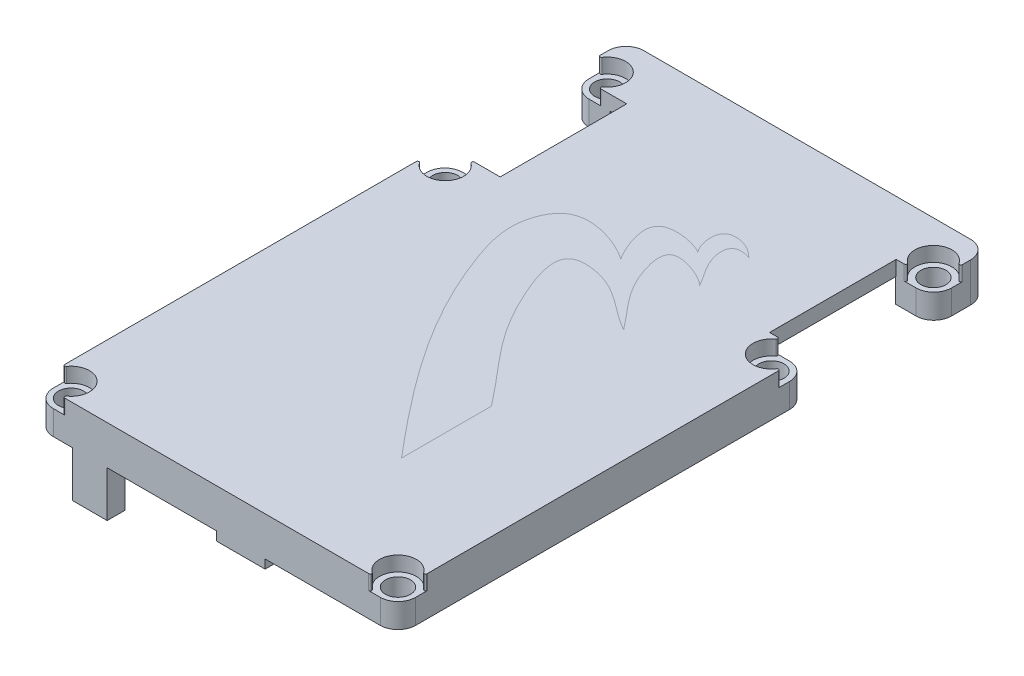
SolidWorks part; units mm, degrees
ref_plane "Front Plane" through (0, 0, 0) normal (0, 0, 1) x (1, 0, 0)
ref_plane "Top Plane" through (0, 0, 0) normal (0, 1, 0) x (1, 0, 0)
ref_plane "Right Plane" through (0, 0, 0) normal (1, 0, 0) x (0, 0, -1)
sketch "Sketch1" plane through (0, 0, 0) normal (0, 1, 0) x (1, 0, 0)
  line L1 (0, 0) -> (49.1, 0)
  line L2 (0, 0) -> (0, -80)
  line L3 (0, -80) -> (49.1, -80)
  line L4 (49.1, 0) -> (49.1, -80)
  dimension "D1" = 80
  dimension "D2" = 49.1
extrude "Boss-Extrude1" add sketch "Sketch1" along normal blind 2
sketch "Sketch2" plane through (0, 2, 0) normal (0, 1, 0) x (1, 0, 0)
  line L0 (49.1, 0) -> (0, 0) construction
  line L1 (2.45, -5) -> (46.65, -5) construction
  line L2 (2.45, -5) -> (2.45, -26.95) construction
  line L3 (2.45, -26.95) -> (46.65, -26.95) construction
  line L4 (46.65, -5) -> (46.65, -26.95) construction
  line L5 (0, 0) -> (0, -80) construction
  line L6 (24.55, -5) -> (24.55, 0) construction
  line L7 (0, -80) -> (49.1, -80) construction
  line L8 (24.55, -80) -> (24.55, -37.9836) construction
  circle A0 centre (2.4, -77.6) radius 1.7
  circle A1 centre (2.45, -26.95) radius 1.7
  circle A2 centre (2.45, -5) radius 1.7
  circle A3 centre (46.7, -77.6) radius 1.7
  circle A4 centre (46.65, -26.95) radius 1.7
  circle A5 centre (46.65, -5) radius 1.7
  dimension "D5" = 3.4
  dimension "D6" = 2.4
  dimension "D7" = 2.4
  dimension "D1" = 5
  dimension "D2" = 21.95
  dimension "D3" = 44.2
extrude "Cut-Extrude1" cut sketch "Sketch2" against normal blind 2
sketch "Sketch3" plane through (0, 0, 0) normal (0, -1, 0) x (1, 0, 0)
  line L0 (24.55, 80) -> (24.55, 0) construction
  line L1 (0, 80) -> (5.2, 80)
  line L2 (0, 80) -> (0, 74.8)
  line L3 (0, 74.8) -> (5.2, 74.8)
  line L4 (5.2, 80) -> (5.2, 74.8)
  line L5 (0, 80) -> (49.1, 80) construction
  line L6 (49.1, 0) -> (0, 0) construction
  line L7 (2.45, 26.95) -> (2.45, 5) construction
  line L8 (2.45, 15.975) -> (24.55, 15.975) construction
  line L9 (0, 0) -> (0, 80) construction
  line L10 (5.2, 29.75) -> (0, 29.75)
  line L11 (5.2, 29.75) -> (5.2, 24.55)
  line L12 (5.2, 24.55) -> (0, 24.55)
  line L13 (0, 29.75) -> (0, 24.55)
  line L16 (5.2, 7.4) -> (0, 2.2) construction
  line L17 (5.2, 2.2) -> (0, 7.4) construction
  line L18 (0, 2.2) -> (0, 7.4)
  line L19 (5.2, 7.4) -> (0, 7.4)
  line L20 (5.2, 2.2) -> (5.2, 7.4)
  line L21 (5.2, 2.2) -> (0, 2.2)
  line L22 (43.9, 2.2) -> (49.1, 7.4) construction
  line L23 (43.9, 7.4) -> (49.1, 2.2) construction
  line L24 (43.9, 24.55) -> (49.1, 29.75) construction
  line L25 (43.9, 29.75) -> (49.1, 24.55) construction
  line L26 (46.65, 26.95) -> (46.65, 5) construction
  line L27 (43.9, 2.2) -> (49.1, 2.2)
  line L28 (43.9, 2.2) -> (43.9, 7.4)
  line L29 (43.9, 7.4) -> (49.1, 7.4)
  line L30 (49.1, 2.2) -> (49.1, 7.4)
  line L31 (49.1, 29.75) -> (49.1, 24.55)
  line L32 (43.9, 24.55) -> (49.1, 24.55)
  line L33 (43.9, 29.75) -> (43.9, 24.55)
  line L34 (43.9, 29.75) -> (49.1, 29.75)
  line L35 (43.9, 80) -> (43.9, 74.8)
  line L36 (49.1, 74.8) -> (43.9, 74.8)
  line L37 (49.1, 80) -> (49.1, 74.8)
  line L38 (49.1, 80) -> (43.9, 80)
  circle A0 centre (2.4, 77.6) radius 1.7
  circle A1 centre (2.4, 77.6) radius 1.7 construction
  circle A2 centre (2.45, 26.95) radius 1.7
  circle A3 centre (2.45, 26.95) radius 1.7 construction
  circle A4 centre (2.45, 5) radius 1.7
  circle A5 centre (46.65, 5) radius 1.7
  circle A6 centre (46.65, 26.95) radius 1.7
  circle A7 centre (46.7, 77.6) radius 1.7
  dimension "D1" = 5.2
  dimension "D2" = 2.4
  dimension "D3" = 2.8
  dimension "D4" = 5.2
  dimension "D5" = 5.2
extrude "Boss-Extrude2" add sketch "Sketch3" along normal blind 3.3
sketch "Sketch4" plane through (0, 2, 0) normal (0, 1, 0) x (1, 0, 0)
  line L0 (0, 0) -> (0, -80) construction
  line L1 (0, -7.4) -> (7.5, -7.4)
  line L2 (0, -7.4) -> (0, -24.55)
  line L3 (0, -24.55) -> (7.5, -24.55)
  line L4 (7.5, -7.4) -> (7.5, -24.55)
  line L5 (2.45, -5) -> (2.45, -26.95) construction
  line L6 (2.45, -15.975) -> (7.5, -15.975) construction
  line L7 (49.1, -80) -> (49.1, 0) construction
  line L8 (49.1, -7.4) -> (44, -7.4)
  line L9 (49.1, -7.4) -> (49.1, -24.55)
  line L10 (49.1, -24.55) -> (44, -24.55)
  line L11 (44, -7.4) -> (44, -24.55)
  line L12 (44, -15.975) -> (7.5, -15.975) construction
  line L13 (5.2, -7.4) -> (0, -7.4) construction
  dimension "D1" = 7.5
  dimension "D4" = 5.1
extrude "Cut-Extrude2" cut sketch "Sketch4" against normal blind 3.3
sketch "Sketch6" plane through (0, 0, 0) normal (0, -1, 0) x (1, 0, 0)
  line L0 (49.1, 46.0108) -> (0, 46.0108) construction
  line L5 (11.8806, 53.3353) -> (37.2194, 53.3353)
  line L6 (11.8806, 53.3353) -> (11.8806, 38.6862)
  line L7 (11.8806, 38.6862) -> (37.2194, 38.6862)
  line L8 (37.2194, 53.3353) -> (37.2194, 38.6862)
  line L9 (11.8806, 53.3353) -> (37.2194, 38.6862) construction
  line L10 (11.8806, 38.6862) -> (37.2194, 53.3353) construction
  line L11 (49.1, 74.8) -> (49.1, 29.75) construction
  line L12 (0, 29.75) -> (0, 74.8) construction
  line L13 (24.55, 80) -> (24.55, 12.0215) construction
  line L14 (5.2, 80) -> (43.9, 80) construction
  point P4 (24.55, 46.0108)
extrude "Boss-Extrude3" [suppressed] add sketch "Sketch6" along normal blind 3.2
sketch "Sketch7" plane through (0, 0, 0) normal (0, -1, 0) x (1, 0, 0)
  line L1 (5.2, 80) -> (43.9, 80)
  line L2 (5.2, 80) -> (5.2, 77.6)
  line L3 (5.2, 77.6) -> (43.9, 77.6)
  line L4 (43.9, 80) -> (43.9, 77.6)
  line L6 (46.7, 74.8) -> (49.1, 74.8)
  line L7 (46.7, 74.8) -> (46.7, 29.75)
  line L8 (46.7, 29.75) -> (49.1, 29.75)
  line L9 (49.1, 74.8) -> (49.1, 29.75)
  line L11 (2.4, 74.8) -> (0, 74.8)
  line L12 (2.4, 74.8) -> (2.4, 29.75)
  line L13 (2.4, 29.75) -> (0, 29.75)
  line L14 (0, 74.8) -> (0, 29.75)
  line L15 (49.1, 2.2) -> (49.1, 0) construction
  line L16 (0, 0) -> (49.1, 0)
  line L17 (0, 0) -> (0, 2)
  line L18 (5.2, 2) -> (43.9, 2)
  line L19 (49.1, 0) -> (49.1, 2)
  line L20 (5.2, 2.2) -> (5.2, 7.4) construction
  line L21 (0, 2.2) -> (5.2, 2.2)
  line L22 (0, 2.2) -> (0, 2)
  line L24 (5.2, 2.2) -> (5.2, 2)
  line L25 (0, 2.2) -> (5.2, 2.2) construction
  line L26 (0, 74.8) -> (5.2, 74.8) construction
  line L28 (49.1, 2) -> (49.1, 2.2)
  line L29 (49.1, 2.2) -> (43.9, 2.2)
  line L30 (43.9, 2) -> (43.9, 2.2)
  line L31 (43.9, 74.8) -> (49.1, 74.8) construction
  dimension "D1" = 2
  dimension "D2" = 2
  dimension "D3" = 2.4
  dimension "D4" = 2.4
  dimension "D5" = 2.4
extrude "Boss-Extrude4" add sketch "Sketch7" along normal up to surface (3.3 mm away) up to face at (46.5, -3.3, 27.15)
sketch "Sketch8" plane through (0, 0, 80) normal (0, 0, 1) x (1, 0, 0)
  line L0 (49.1, -3.3) -> (0, -3.3) construction
  line L1 (24.5, -3.3) -> (31.1, -3.3)
  line L2 (24.5, -3.3) -> (24.5, -4.5)
  line L3 (24.5, -4.5) -> (31.1, -4.5)
  line L4 (31.1, -3.3) -> (31.1, -4.5)
  line L6 (27.8, -4.5) -> (27.8, 0) construction
  line L7 (49.1, 2) -> (49.1, -3.3) construction
  line L8 (5, -3.3) -> (9.7, -3.3)
  line L9 (5, -3.3) -> (5, -9.5)
  line L10 (5, -9.5) -> (9.7, -9.5)
  line L11 (9.7, -3.3) -> (9.7, -9.5)
  line L12 (7.35, -9.5) -> (7.35, 5.3073) construction
  line L13 (0, 2) -> (0, -3.3) construction
  dimension "D1" = 1.2
  dimension "D2" = 6.6
  dimension "D3" = 21.3
  dimension "D4" = 6.2
  dimension "D5" = 7.35
  dimension "D6" = 4.7
extrude "Boss-Extrude5" add sketch "Sketch8" against normal up to surface (2.4 mm away) up to face at (24.55, -1.65, 77.6)
fillet "Fillet1" radius 2.4 8 edges at (0, -0.65, 24.55) (0, -0.65, 7.4) (0, -0.65, 0) (49.1, -0.65, 0) (49.1, -0.65, 80) (0, -0.65, 80) (49.1, -0.65, 7.4) (49.1, -0.65, 24.55)
sketch "Sketch9" plane through (0, 2, 0) normal (0, 1, 0) x (1, 0, 0)
  line L0 (24.55, 0) -> (24.55, -80) construction
  line L1 (46.7, 0) -> (2.4, 0) construction
  line L2 (2.4, -80) -> (46.7, -80) construction
  circle A0 centre (2.45, -5) radius 2.5
  circle A1 centre (2.45, -26.95) radius 2.5
  circle A2 centre (2.4, -77.6) radius 2.5
  circle A3 centre (46.7, -77.6) radius 2.5
  circle A4 centre (46.65, -26.95) radius 2.5
  circle A5 centre (46.65, -5) radius 2.5
  dimension "D1" = 5
extrude "Cut-Extrude3" cut sketch "Sketch9" against normal blind 2
fillet "Fillet2" radius 0.2 12 edges at (45.95, 1, 7.4) (45.95, 1, 24.55) (49.1, 1, 27.4475) (46, 1, 80) (0, 1, 27.4475) (3.15, 1, 24.55) (3.15, 1, 7.4) (0, 1, 4.5025) (49.1, 1, 4.5025) (49.1, 1, 76.9) (3.1, 1, 80) (0, 1, 76.9)
sketch "Sketch10" plane through (0, 2, 0) normal (0, 1, 0) x (1, 0, 0)
  line L0 (-11.5, -29.3333) -> (51.0302, -29.3333) construction
  line L1 (33.8023, -64.2177) -> (33.8023, -52.034)
  spline S0 degree 3 poles (33.8023, -64.2177) (26.3841, -55.4036) (17.6993, -44.3196) (13.3464, -29.0084) (16.8728, -21.8284) (23.563, -24.7245) (25.3089, -26.0213) knots 0 0 0 0 0.620999 0.759293 0.829423 1 1 1 1
  spline S1 degree 3 poles (33.8023, -52.034) (29.1548, -46.0382) (24.9516, -42.819) (19.7219, -28.5902) (28.3588, -29.2536) (30.8501, -32.5158) (33.8023, -34.1257) knots 0 0 0 0 0.482391 0.665596 0.759856 1 1 1 1
  spline S2 degree 3 poles (33.8023, -34.1257) (31.6331, -31.2498) (28.8606, -29.0803) (26.7443, -20.0343) (33.215, -22.9965) (33.8023, -23.8535) knots 0 0 0 0 0.496656 0.690746 1 1 1 1
  spline S3 degree 3 poles (25.3089, -26.0213) (24.4402, -24.7426) (21.1452, -17.601) (28.6744, -19.2394) (29.8757, -20.0845) knots 0 0 0 0 0.51853 1 1 1 1
  spline S4 degree 3 poles (29.8757, -20.0845) (29.026, -19.4884) (28.0649, -15.3885) (32.0308, -15.666) (33.1936, -16.6008) (33.8023, -17.1576) knots 0 0 0 0 0.475368 0.739118 1 1 1 1
  spline S5 degree 3 poles (33.8023, -23.8535) (33.013, -22.4177) (30.9977, -20.2419) (30.9844, -16.2614) (33.8023, -17.1576) knots 0 0 0 0 0.515144 1 1 1 1
  point P7 (31.2937, -17.8032)
  point P19 (31.4679, -19.6971)
  point P33 (28.9227, -17.9673)
  point P35 (27.5372, -19.2141)
split line "Split Line2"
